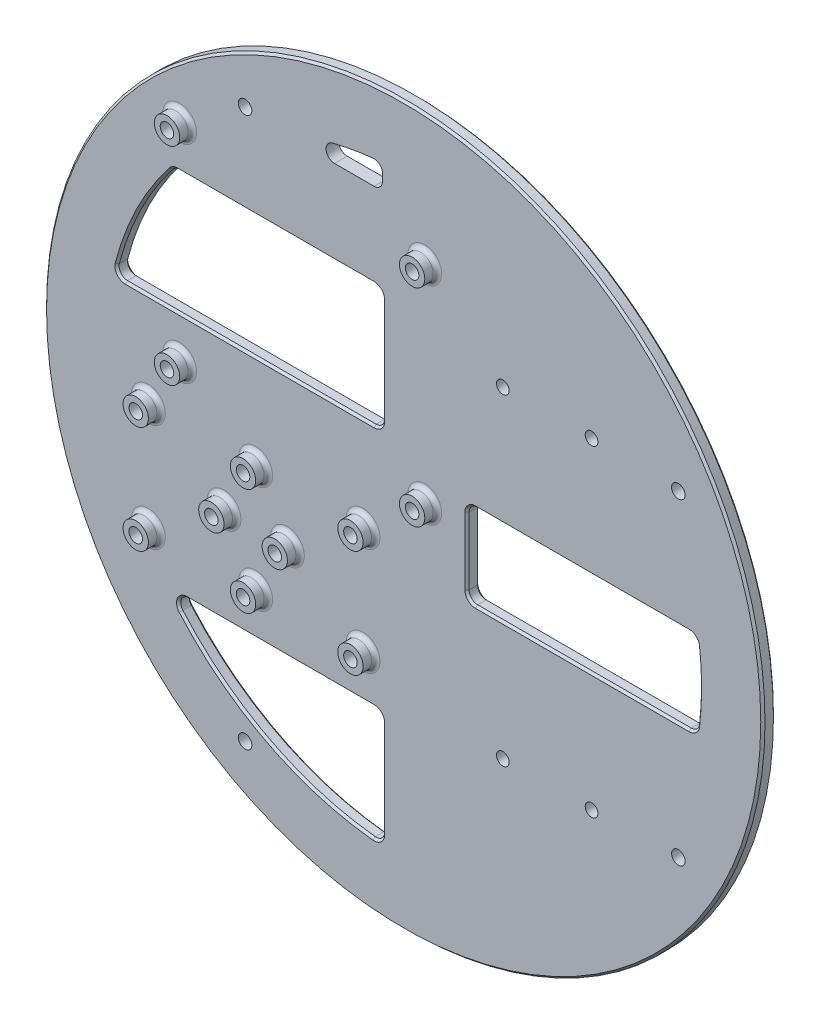
SolidWorks part; units mm, degrees
material "ABS"
ref_plane "Front" through (0, 0, 0) normal (0, 0, 1) x (1, 0, 0)
ref_plane "Top" through (0, 0, 0) normal (0, 1, 0) x (1, 0, 0)
ref_plane "Right" through (0, 0, 0) normal (1, 0, 0) x (0, 0, -1)
sketch "Эскиз1" plane through (0, 0, 0) normal (0, 0, 1) x (1, 0, 0)
  line L0 (0, 0) -> (-45.4321, 78.6908) construction
  line L1 (0, 0) -> (-45.4321, -78.6908) construction
  line L2 (0, 0) -> (78.6908, -45.4321) construction
  line L3 (0, 0) -> (78.6908, 45.4321) construction
  line L4 (-5, 69.8212) -> (-5, 64)
  line L5 (15, 10) -> (15, -10)
  line L6 (-5, -42.7) -> (-55.4681, -42.7)
  line L7 (-5, -42.7) -> (-5, -70)
  line L8 (-5, 15) -> (-68.374, 15)
  line L9 (-5, 64) -> (-28.3549, 64)
  line L10 (-5, 44) -> (-5, 15)
  line L11 (-5, 44) -> (-54.4426, 44)
  line L12 (15, 10) -> (69.282, 10)
  line L13 (15, -10) -> (69.282, -10)
  line L14 (0, 0) -> (87, 0) construction
  line L15 (0, 0) -> (-87, 0) construction
  line L16 (0, 0) -> (0, 87) construction
  line L17 (0, 0) -> (0, -87) construction
  circle A645 centre (0, 0) radius 85
  circle A646 centre (0, 0) radius 75.05 construction
  circle A647 centre (-37.525, 64.9952) radius 1.6
  circle A648 centre (-37.525, -64.9952) radius 1.6
  circle A649 centre (0, 0) radius 75.05 construction
  circle A650 centre (64.9952, -37.525) radius 1.6
  circle A651 centre (64.9952, 37.525) radius 1.6
  circle A652 centre (-53, 5) radius 1.6
  circle A653 centre (-53, 54) radius 1.6
  circle A654 centre (-42.5, -20) radius 1.6
  circle A655 centre (-27.5, -20) radius 1.6
  circle A656 centre (5, 5) radius 1.6
  circle A657 centre (5, 54) radius 1.6
  circle A658 centre (-53, 5) radius 3
  circle A659 centre (5, 5) radius 3
  circle A660 centre (5, 54) radius 3
  circle A661 centre (-42.5, -20) radius 3
  circle A662 centre (-27.5, -20) radius 3
  circle A663 centre (-60.4, -7.3) radius 1.6
  circle A664 centre (-60.4, -7.3) radius 3
  circle A665 centre (-35, -7.3) radius 1.6
  circle A666 centre (-35, -7.3) radius 3
  circle A667 centre (-9.6, -7.3) radius 1.6
  circle A668 centre (-9.6, -7.3) radius 3
  circle A669 centre (-9.6, -32.7) radius 1.6
  circle A670 centre (-9.6, -32.7) radius 3
  circle A671 centre (-35, -32.7) radius 1.6
  circle A672 centre (-35, -32.7) radius 3
  circle A673 centre (-60.4, -32.7) radius 1.6
  circle A674 centre (-60.4, -32.7) radius 3
  arc A675 (-54.4426, 44) -> (-68.374, 15) centre (0, 0) ccw
  arc A676 (-55.4681, -42.7) -> (-5, -69.8212) centre (0, 0) ccw
  arc A677 (-5, 69.8212) -> (-28.3549, 64) centre (0, 0) ccw
  arc A678 (69.282, -10) -> (69.282, 10) centre (0, 0) ccw
  circle A679 centre (23.4612, 38.075) radius 1.5
  circle A680 centre (44.4612, 38.075) radius 1.5
  circle A681 centre (23.4612, -38.075) radius 1.5
  circle A682 centre (44.4612, -38.075) radius 1.5
  circle A683 centre (-53, 54) radius 3
extrude "Бобышка-Вытянуть1" add sketch "Эскиз1" along normal blind 3 contours A645 A683 A682 A681 A680 A679 A678 L13 L5 L12 A677 L4 L9 A676 L6 L7 A675 L11 L10 L8 A674 A672 A670 A668 A666 A664 A662 A661 A660 A659 | A674 A673 | A661 A654 | A672 A671 | A662 A655 | A670 A669 | A668 A667 | A666 A665 | A664 A663 | A658 A652 | A660 A657 | A683 A653 | A659 A656 region at (2.3416, -0.1992, 0) region at (-55.9151, 5, 0) region at (2.0849, 5, 0) region at (2.0849, 54, 0) region at (-45.4151, -20, 0) region at (-30.4151, -20, 0) region at (-63.3151, -7.3, 0) region at (-37.9151, -7.3, 0) region at (-12.5151, -7.3, 0) region at (-12.5151, -32.7, 0) region at (-37.9151, -32.7, 0) region at (-63.3151, -32.7, 0) region at (-55.9151, 54, 0)
fillet "Скругление1" radius 2 14 edges at (-5, -69.8212, 1.5) (-5, -42.7, 1.5) (-55.4681, -42.7, 1.5) (15, -10, 1.5) (15, 10, 1.5) (69.282, -10, 1.5) (69.282, 10, 1.5) (-5, 69.8212, 1.5) (-28.3549, 64, 1.5) (-5, 64, 1.5) (-5, 15, 1.5) (-68.374, 15, 1.5) (-54.4426, 44, 1.5) (-5, 44, 1.5)
extrude "Бобышка-Вытянуть2" add sketch "Эскиз1<3>" along normal blind 6 contours A674 A673 | A661 A654 | A666 A665 | A664 A663 | A658 A652 | A668 A667 | A662 A655 | A672 A671 | A670 A669 | A659 A656 | A660 A657 | A683 A653 region at (-55.9151, 5, 0) region at (2.0849, 5, 0) region at (2.0849, 54, 0) region at (-45.4151, -20, 0) region at (-30.4151, -20, 0) region at (-63.3151, -7.3, 0) region at (-37.9151, -7.3, 0) region at (-12.5151, -7.3, 0) region at (-12.5151, -32.7, 0) region at (-37.9151, -32.7, 0) region at (-63.3151, -32.7, 0) region at (-55.9151, 54, 0)
sketch "Эскиз1<3>" plane through (0, 0, 0) normal (0, 0, 1) x (1, 0, 0) same geometry as "Эскиз1"
fillet "Скругление2" radius 1 12 edges at (-6.6, -32.7, 3) (8, 5, 3) (-6.6, -7.3, 3) (-24.5, -20, 3) (-32, -32.7, 3) (-39.5, -20, 3) (-57.4, -32.7, 3) (-50, 5, 3) (-57.4, -7.3, 3) (-32, -7.3, 3) (8, 54, 3) (-50, 54, 3)
chamfer "Фаска1" distance 0.5 angle 45 2 edges at (85, 0, 0) (85, 0, 3)
chamfer "Фаска2" distance 0.5 angle 45 44 edges at (42.2639, -10, 0) (15.5858, -9.4142, 0) (68.8562, -9.4951, 0) (15, 0, 0) (70, 0, 0) (15.5858, 9.4142, 0) (68.8562, 9.4951, 0) (42.2639, 10, 0) (-30.2395, 44, 0) (-5.5858, 43.4142, 0) (-54.3534, 43.7987, 0) (-5, 29.5, 0) (-62.7481, 31.027, 0) (-5.5858, 15.5858, 0) (-67.4219, 15.7753, 0) (-36.4204, 15, 0) (-5.6606, -69.124, 0) (-5, -56.1694, 0) (-32.2195, -62.1442, 0) (-5.5858, -43.2858, 0) (-53.0643, -43.8722, 0) (-29.1218, -42.7, 0) (-5.6606, -69.124, 3) (-5, -56.1694, 3) (-32.2195, -62.1442, 3) (-5.5858, -43.2858, 3) (-53.0643, -43.8722, 3) (-29.1218, -42.7, 3) (42.2639, -10, 3) (15.5858, -9.4142, 3) (68.8562, -9.4951, 3) (15, 0, 3) (70, 0, 3) (15.5858, 9.4142, 3) (68.8562, 9.4951, 3) (42.2639, 10, 3) (-36.4204, 15, 3) (-5.5858, 15.5858, 3) (-67.4219, 15.7753, 3) (-5, 29.5, 3) (-62.7481, 31.027, 3) (-5.5858, 43.4142, 3) (-54.3534, 43.7987, 3) (-30.2395, 44, 3)
